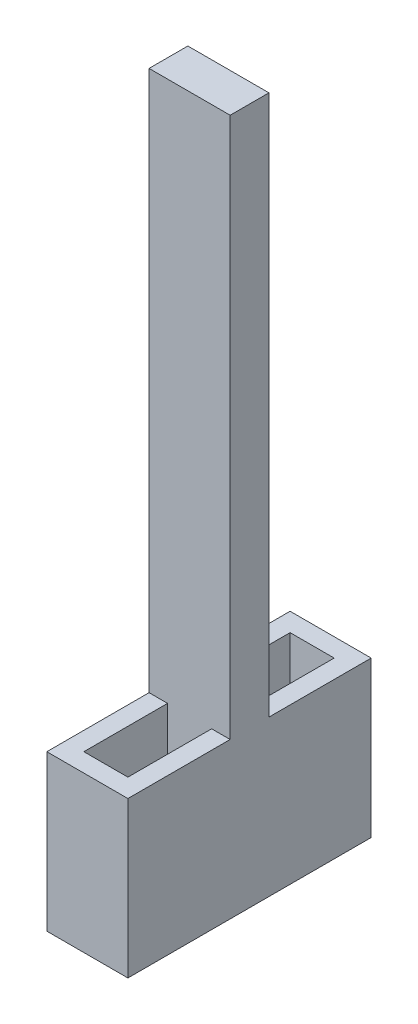
SolidWorks part; units mm, degrees
ref_plane "Front Plane" through (0, 0, 0) normal (0, 0, 1) x (1, 0, 0)
ref_plane "Top Plane" through (0, 0, 0) normal (0, 1, 0) x (1, 0, 0)
ref_plane "Right Plane" through (0, 0, 0) normal (1, 0, 0) x (0, 0, -1)
sketch "Sketch1" plane through (0, 0, 0) normal (0, 1, 0) x (1, 0, 0)
  line L0 (-3, 3) -> (-3, 9)
  line L1 (-3, 9) -> (3, 9)
  line L2 (3, 9) -> (3, 3)
  line L3 (3, 3) -> (9, 3)
  line L4 (9, 3) -> (9, -3)
  line L5 (9, -3) -> (3, -3)
  line L6 (3, -3) -> (3, -9)
  line L7 (3, -9) -> (-3, -9)
  line L8 (-3, -9) -> (-3, -3)
  line L9 (-3, -3) -> (-9, -3)
  line L10 (-9, -3) -> (-9, 3)
  line L11 (-9, 3) -> (-3, 3)
  point P13 (-9, 0)
  point P14 (0, 9)
  dimension "D1" = 6
  dimension "D2" = 6
extrude "Boss-Extrude1" add sketch "Sketch1" along normal blind 1.5
sketch "Sketch3" plane through (0, 1.5, 0) normal (0, 1, 0) x (1, 0, 0)
  line L0 (-1.63, 1.63) -> (-7.63, 1.63)
  line L1 (-7.63, 1.63) -> (-7.63, -1.63)
  line L2 (-7.63, -1.63) -> (-1.63, -1.63)
  line L3 (-1.63, -1.63) -> (-1.63, -7.63)
  line L4 (-1.63, -7.63) -> (1.63, -7.63)
  line L5 (1.63, -7.63) -> (1.63, -1.63)
  line L6 (1.63, -1.63) -> (7.63, -1.63)
  line L7 (7.63, -1.63) -> (7.63, 1.63)
  line L8 (7.63, 1.63) -> (1.63, 1.63)
  line L9 (1.63, 1.63) -> (1.63, 7.63)
  line L10 (1.63, 7.63) -> (-1.63, 7.63)
  line L11 (-1.63, 7.63) -> (-1.63, 1.63)
  line L12 (-3, 3) -> (-9, 3)
  line L13 (-9, 3) -> (-9, -3)
  line L14 (-9, -3) -> (-3, -3)
  line L15 (-3, -3) -> (-3, -9)
  line L16 (-3, -9) -> (3, -9)
  line L17 (3, -9) -> (3, -3)
  line L18 (3, -3) -> (9, -3)
  line L19 (9, -3) -> (9, 3)
  line L20 (9, 3) -> (3, 3)
  line L21 (3, 3) -> (3, 9)
  line L22 (3, 9) -> (-3, 9)
  line L23 (-3, 9) -> (-3, 3)
  line L24 (-3, 3) -> (-9, 3)
  line L25 (-9, 3) -> (-9, -3)
  line L26 (-9, -3) -> (-3, -3)
  line L27 (-3, -3) -> (-3, -9)
  line L28 (-3, -9) -> (3, -9)
  line L29 (3, -9) -> (3, -3)
  line L30 (3, -3) -> (9, -3)
  line L31 (9, -3) -> (9, 3)
  line L32 (9, 3) -> (3, 3)
  line L33 (3, 3) -> (3, 9)
  line L34 (3, 9) -> (-3, 9)
  line L35 (-3, 9) -> (-3, 3)
  dimension "D2" = 1.37
extrude "Boss-Extrude5" add sketch "Sketch3" along normal blind 10
sketch "Sketch2" plane through (0, 1.5, 0) normal (0, 1, 0) x (1, 0, 0)
  line L1 (-1.435, 1.435) -> (1.435, 1.435)
  line L2 (-1.435, 1.435) -> (-1.435, -1.435)
  line L3 (-1.435, -1.435) -> (1.435, -1.435)
  line L4 (1.435, 1.435) -> (1.435, -1.435)
  point P4 (-1.435, 0)
  point P5 (0, 1.435)
  dimension "D1" = 2.87
extrude "Boss-Extrude2" add sketch "Sketch2" along normal blind 10
sketch "Sketch4" plane through (0, 11.5, 0) normal (0, 1, 0) x (1, 0, 0)
  line L1 (-9, 3) -> (-3, 3)
  line L2 (-9, 3) -> (-9, -3)
  line L3 (-9, -3) -> (-3, -3)
  line L4 (-3, 3) -> (-3, -3)
extrude "Cut-Extrude1" cut sketch "Sketch4" against normal through all
sketch "Sketch5" plane through (0, 11.5, 0) normal (0, 1, 0) x (1, 0, 0)
  line L0 (-1.435, 1.435) -> (-1.435, -1.435) construction
  line L1 (-3, 1.63) -> (-1.63, 1.63)
  line L2 (-3, 1.63) -> (-3, -1.63)
  line L3 (-3, -1.63) -> (-1.63, -1.63)
  line L4 (-1.63, 1.63) -> (-1.63, 1.435)
  line L5 (-1.435, 1.435) -> (-1.63, 1.435)
  line L6 (-1.435, 1.435) -> (-1.435, -1.435)
  line L7 (-1.435, -1.435) -> (-1.63, -1.435)
  line L9 (1.435, 1.435) -> (-1.435, 1.435) construction
  line L10 (-1.435, -1.435) -> (1.435, -1.435) construction
  line L11 (-1.63, -1.435) -> (-1.63, -1.63)
extrude "Boss-Extrude6" add sketch "Sketch5" against normal blind 10
sketch "Sketch6" [suppressed] plane through (0, 12, 0) normal (0, 1, 0) x (1, 0, 0)
  line L1 (-3.5, 11.5) -> (3.5, 11.5)
  line L2 (-3.5, 11.5) -> (-3.5, 3.5)
  line L3 (-3.5, 3.5) -> (3.5, 3.5)
  line L4 (3.5, 11.5) -> (3.5, 3.5)
extrude "Cut-Extrude2" [suppressed] cut sketch "Sketch6" against normal through all
sketch "Sketch7" [suppressed] plane through (0, 12, 0) normal (0, 1, 0) x (1, 0, 0)
  line L0 (1.4, 1.4) -> (-1.7, 1.4) construction
  line L1 (-1.7, 3.5) -> (-1.7, 1.4) construction
  line L2 (-1.7, 3.5) -> (1.7, 3.5) construction
  line L3 (1.4, 1.4) -> (-1.7, 1.4)
  line L4 (-1.7, 3.5) -> (-1.7, 1.4)
  line L5 (-1.7, 3.5) -> (1.7, 3.5)
  line L8 (1.7, 3.5) -> (1.7, 1.7)
  line L9 (1.7, 1.7) -> (1.4, 1.7)
  line L10 (1.4, 1.7) -> (1.4, 1.4)
extrude "Boss-Extrude7" [suppressed] add sketch "Sketch7" against normal blind 10
sketch "Sketch8" plane through (0, 11.5, 0) normal (0, 1, 0) x (1, 0, 0)
  line L1 (3, 3) -> (9, 3)
  line L2 (3, 3) -> (3, -3)
  line L3 (3, -3) -> (9, -3)
  line L4 (9, 3) -> (9, -3)
extrude "Cut-Extrude3" cut sketch "Sketch8" against normal through all
sketch "Sketch9" plane through (0, 11.5, 0) normal (0, 1, 0) x (1, 0, 0)
  line L0 (1.435, -1.435) -> (1.435, 1.435) construction
  line L1 (3, 1.63) -> (1.63, 1.63) construction
  line L2 (3, 1.63) -> (3, -1.63) construction
  line L3 (1.63, -1.63) -> (3, -1.63) construction
  line L4 (1.435, -1.435) -> (1.435, 1.435)
  line L5 (3, 1.63) -> (1.63, 1.63)
  line L6 (3, 1.63) -> (3, -1.63)
  line L7 (1.63, -1.63) -> (3, -1.63)
  line L8 (1.435, 1.435) -> (1.63, 1.435)
  line L9 (1.63, 1.435) -> (1.63, 1.63)
  line L10 (1.435, -1.435) -> (1.63, -1.435)
  line L11 (1.63, -1.435) -> (1.63, -1.63)
extrude "Boss-Extrude8" add sketch "Sketch9" against normal blind 10
sketch "Sketch10" plane through (0, 11.5, 0) normal (0, 1, 0) x (1, 0, 0)
  line L4 (-3, 9) -> (-3, -9)
  line L12 (-3, 9) -> (-3, -9)
  line L15 (-3, -9) -> (3, -9)
  line L18 (-3, -9) -> (3, -9)
  line L20 (3, -9) -> (3, 9)
  line L21 (3, -9) -> (3, 9)
  line L22 (3, 9) -> (-3, 9)
  line L23 (3, 9) -> (-3, 9)
  dimension "D1" = 0
extrude "Boss-Extrude9" [suppressed] add sketch "Sketch10" along normal blind 40
sketch "Sketch11" plane through (0, 11.5, 0) normal (0, 1, 0) x (1, 0, 0)
  line L0 (-3, 9) -> (-3, -9) construction
  line L5 (1.63, 1.435) -> (-3, 1.435)
  line L6 (1.63, 1.435) -> (1.63, -1.435)
  line L7 (1.63, -1.435) -> (-3, -1.435)
  line L8 (-3, 1.435) -> (-3, -1.435)
  line L9 (-1.63, -1.435) -> (1.63, -1.435) construction
extrude "Boss-Extrude10" [suppressed] add sketch "Sketch11" along normal blind 40
sketch "Sketch12" [suppressed] plane through (0, 11.5, 0) normal (0, 1, 0) x (1, 0, 0)
  line L0 (-1.6, -1.45) -> (1.45, -1.45) construction
  line L1 (1.45, -1.45) -> (-3, -1.45)
  line L2 (1.45, -1.45) -> (1.45, 3)
  line L3 (1.45, 3) -> (-3, 3)
  line L4 (-3, -1.45) -> (-3, 3)
  line L5 (1.45, -1.45) -> (1.45, 1.6) construction
extrude "Boss-Extrude11" [suppressed] add sketch "Sketch12" along normal blind 40
sketch "Sketch13" plane through (0, 11.5, 0) normal (0, 1, 0) x (1, 0, 0)
  line L0 (-3, 9) -> (-3, -9) construction
  line L1 (-3, 1.435) -> (3, 1.435)
  line L2 (-3, 1.435) -> (-3, -1.435)
  line L3 (-3, -1.435) -> (3, -1.435)
  line L4 (3, 1.435) -> (3, -1.435)
  line L5 (3, -9) -> (3, 9) construction
  line L7 (1.63, 1.435) -> (-1.63, 1.435) construction
  line L8 (-1.63, -1.435) -> (1.63, -1.435) construction
extrude "Boss-Extrude12" add sketch "Sketch13" along normal blind 40
equation "\"mdfWidth\"= 3"
equation "\"cellSide\"= 180"
equation "\"mazeHeight\"= 50"
equation "\"slitHeight\"= 10"
equation "\"gripWidth\"= 6"
equation "\"wallThickness\"= 1.5"
equation "\"slitWidth\"= \"wallThickness\""
equation "\"D1@Sketch1\"= \"mdfWidth\" + 2 * \"wallThickness\""
equation "\"D2@Sketch1\"=\"gripWidth\""
equation "\"D1@Boss-Extrude1\"= \"wallThickness\""
equation "\"D1@Boss-Extrude2\"= \"slitHeight\""
equation "\"D2@Sketch3\"=\"wallThickness\" - \"jeu\""
equation "\"D1@Boss-Extrude5\"= \"slitHeight\""
equation "\"jeu\"= 0.13"
equation "\"D1@Sketch2\"=\"mdfWidth\"- \"jeu\""
equation "\"D1@Boss-Extrude6\"= \"slitHeight\""
equation "\"D1@Boss-Extrude7\"= \"slitHeight\""
equation "\"D1@Boss-Extrude8\"= \"slitHeight\""
equation "\"D1@Boss-Extrude9\"= \"mazeHeight\" - \"slitHeight\""
equation "\"D1@Boss-Extrude10\"= \"mazeHeight\" - \"slitHeight\""
equation "\"D1@Boss-Extrude11\"= \"mazeHeight\" - \"slitHeight\""
equation "\"D1@Boss-Extrude12\"= \"mazeHeight\" - \"slitHeight\""
